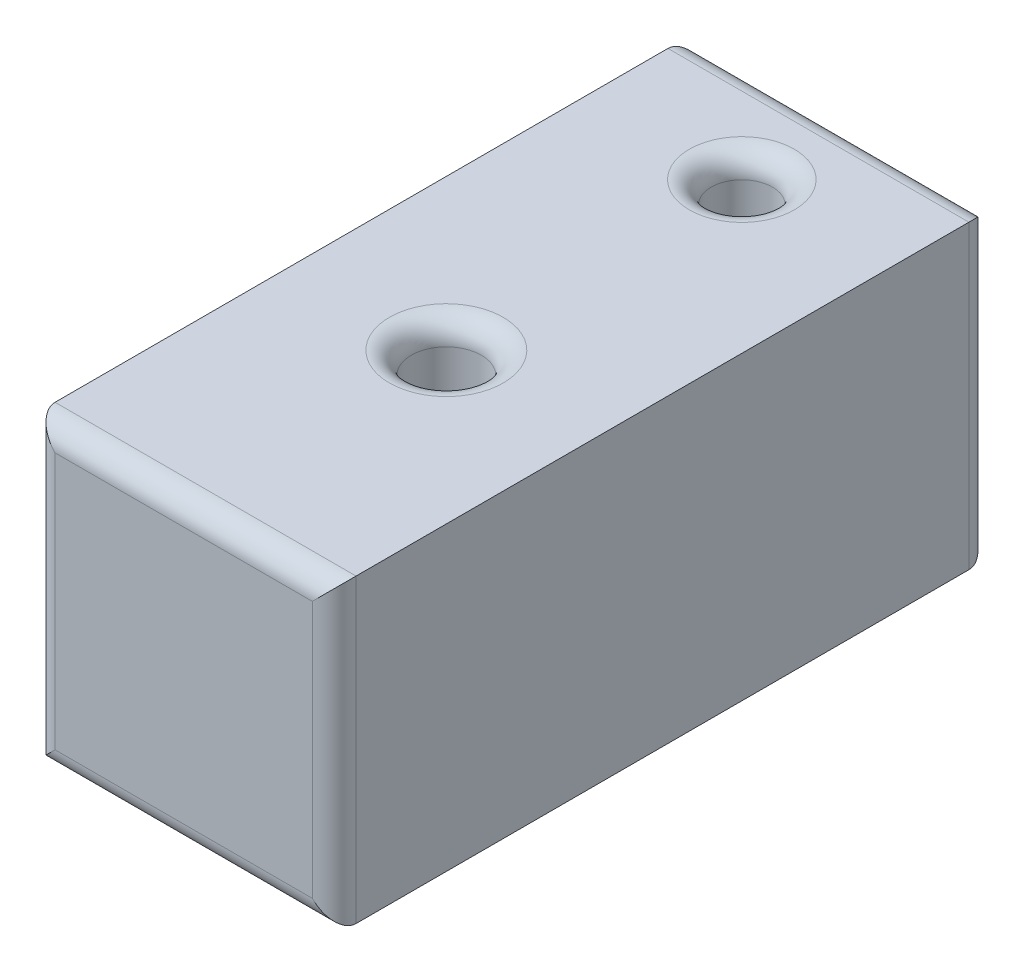
SolidWorks part; units mm, degrees
ref_plane "Front Plane" through (0, 0, 0) normal (0, 0, 1) x (1, 0, 0)
ref_plane "Top Plane" through (0, 0, 0) normal (0, 1, 0) x (1, 0, 0)
ref_plane "Right Plane" through (0, 0, 0) normal (1, 0, 0) x (0, 0, -1)
sketch "Sketch1" plane through (0, 0, 0) normal (0, 0, 1) x (1, 0, 0)
  line L1 (-6.875, -6.875) -> (6.875, -6.875)
  line L2 (-6.875, -6.875) -> (-6.875, 6.875)
  line L3 (-6.875, 6.875) -> (6.875, 6.875)
  line L4 (6.875, -6.875) -> (6.875, 6.875)
  line L5 (-6.875, -6.875) -> (6.875, 6.875) construction
  line L6 (-6.875, 6.875) -> (6.875, -6.875) construction
  point P0 (0, 0)
  dimension "D1" = 13.75
extrude "Boss-Extrude1" add sketch "Sketch1" along normal blind 12 and the other way blind 18
sketch "Sketch2" plane through (0, 0, 0) normal (0, 1, 0) x (1, 0, 0)
  circle A0 centre (0, 0) radius 1.6
  arc A3 (0, 14.525) -> (0, 12.475) centre (0, 13.5) ccw construction
  arc A4 (0, 14.525) -> (0, 12.475) centre (0, 13.5) ccw construction
  circle A5 centre (0, 13.5) radius 1.4
  dimension "D1" = 3.2
  dimension "D2" = 2.8
extrude "Cut-Extrude1" cut sketch "Sketch2" against normal through all and the other way through all
fillet "Fillet1" radius 1 8 edges at (0, 6.875, -18) (-6.875, 0, -18) (0, -6.875, -18) (6.875, 0, -18) (0, -6.875, 12) (-6.875, 0, 12) (0, 6.875, 12) (6.875, 0, 12)
fillet "Fillet2" radius 1 4 edges at (0, 6.875, -12.1) (0, -6.875, -12.1) (0, -6.875, 1.6) (0, 6.875, 1.6)
